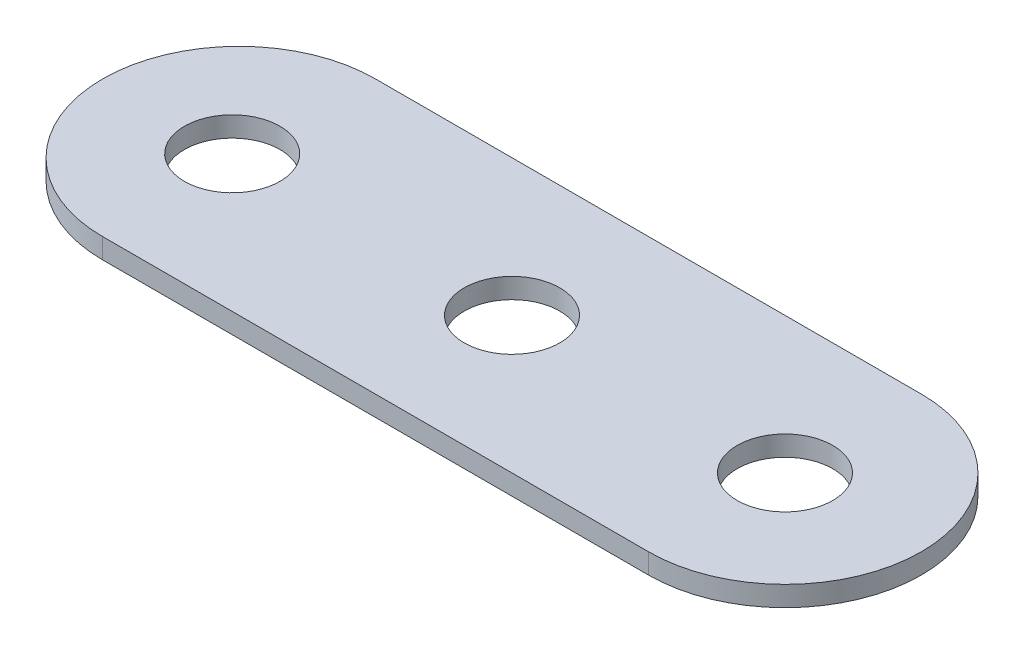
SolidWorks part; units mm, degrees
ref_plane "Front Plane" through (0, 0, 0) normal (0, 0, 1) x (1, 0, 0)
ref_plane "Top Plane" through (0, 0, 0) normal (0, 1, 0) x (1, 0, 0)
ref_plane "Right Plane" through (0, 0, 0) normal (1, 0, 0) x (0, 0, -1)
ref_plane "Plane1"
sketch "Sketch1" plane through (0, 0, 0) normal (0, 1, 0) x (-1, 0, 0)
  line L0 (62.865, -6.35) -> (37.465, -6.35)
  line L1 (62.865, 6.35) -> (37.465, 6.35)
  arc A0 (62.865, -6.35) -> (62.865, 6.35) centre (62.865, 0) ccw
  arc A1 (37.465, -6.35) -> (37.465, 6.35) centre (37.465, 0) cw
  circle A2 centre (37.465, 0) radius 2.2225
  circle A3 centre (63.1825, 0) radius 2.2225
  circle A4 centre (50.165, 0) radius 2.2225
  dimension "D1" = 12.7
  dimension "D3" = 4.445
  dimension "D5" = 4.445
  dimension "D6" = 12.7
  dimension "D7" = 6.35
  dimension "D8" = 6.35
  dimension "D2" = 6.35
  dimension "D4" = 4.445
extrude "Bar" add sketch "Sketch1" along normal blind 0.9398 contours A0 A3 A4 region at (-50.165, 0, -5.9484)
ref_plane "Plane2" through (0, 0.9398, 0) normal (0, 1, 0) x (1, 0, 0)
sketch "Sketch2" plane through (0, 0.9398, 0) normal (0, 1, 0) x (1, 0, 0)
  circle A0 centre (-50.165, 0) radius 2.2225
  dimension "D1" = 12.7
ref_plane "Plane3" through (0, 0, 0) normal (0, -1, 0) x (-1, 0, 0)
ref_plane "Plane4" through (0, 0, 0) normal (0, 0, 1) x (1, 0, 0)
ref_axis "Axis1" through (-80.9, 0, 0) along (1, 0, 0)
